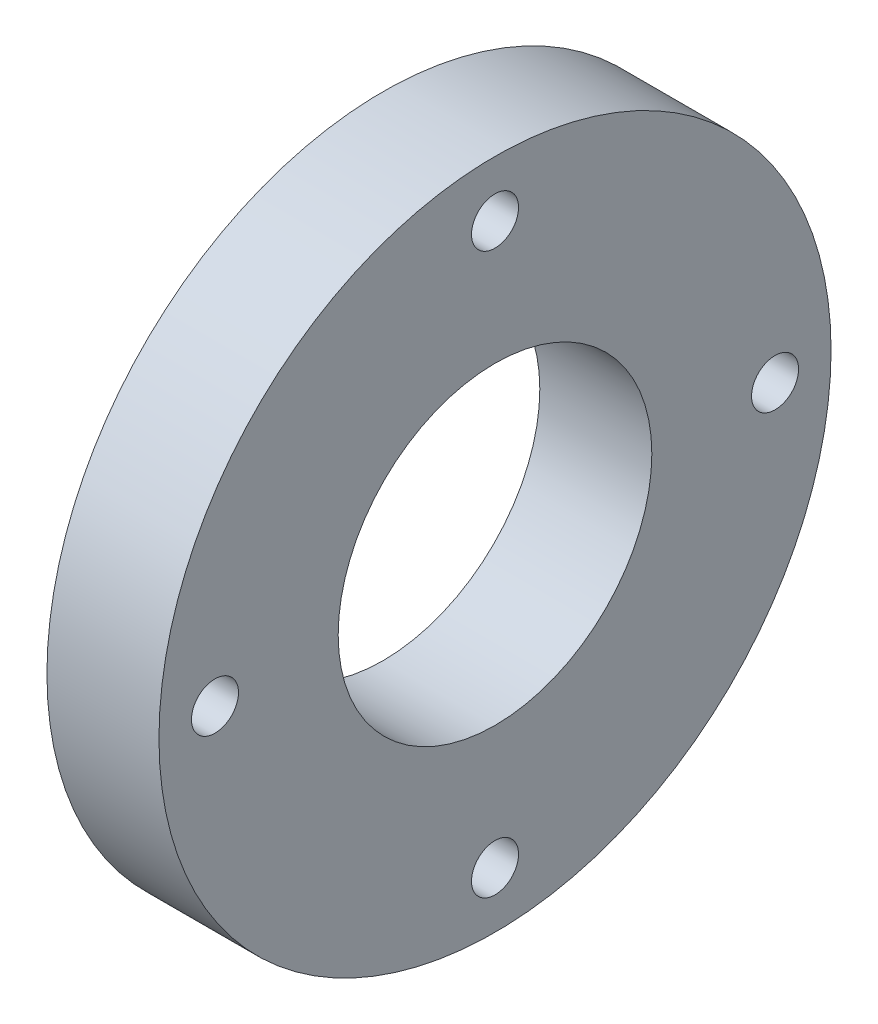
SolidWorks part; units mm, degrees
ref_plane "Front Plane" through (0, 0, 0) normal (0, 0, 1) x (1, 0, 0)
ref_plane "Top Plane" through (0, 0, 0) normal (0, 1, 0) x (1, 0, 0)
ref_plane "Right Plane" through (0, 0, 0) normal (1, 0, 0) x (0, 0, -1)
sketch "Sketch1" plane through (0, 0, 0) normal (0, 0, 1) x (1, 0, 0)
  line L0 (21, 15) -> (21, 0)
  line L1 (21, 0) -> (26, 0)
  line L2 (26, 0) -> (26, 15)
  line L3 (26, 15) -> (21, 15)
  line L4 (21, 0) -> (26, 0) construction
revolve "Revolve1" add sketch "Sketch1" angle 360 about L4 reverse direction yes
hole_wizard "Ø14.0 (14) Diameter Hole1" positions "Sketch3" profile "Sketch2" hole size "Ø14.0" standard "ANSI Metric"
sketch "Sketch3" plane through (21, 0, 0) normal (-1, 0, 0) x (0, 0, 1)
  point P0 (0, 0)
sketch "Sketch2" plane through (21, 0, 0) normal (0, 1, 0) x (0, 0, 1)
  line L0 (0, 0) -> (0, 5)
  line L1 (0, 5) -> (7, 5)
  line L2 (7, 5) -> (7, 0)
  line L5 (7, 0) -> (0, 0)
  line L11 (0, -6.35) -> (0, 107.95) construction
  dimension "Thru Hole Dia." = 14
  dimension "Thru Hole Depth" = 5
hole_wizard "Ø2.1 (2.1) Diameter Hole1" positions "Sketch5" profile "Sketch4" hole size "Ø2.1" standard "ANSI Metric"
sketch "Sketch5" plane through (26, 0, 0) normal (1, 0, 0) x (0, 0, -1)
  point P0 (-12.5, 0)
  point P1 (12.5, 0)
  point P2 (0, -12.5)
  point P3 (0, 12.5)
sketch "Sketch4" plane through (26, 0, 12.5) normal (0, 1, 0) x (0, 0, -1)
  line L0 (0, 0) -> (0, 2.5)
  line L1 (0, 2.5) -> (1.05, 2.5)
  line L2 (1.05, 2.5) -> (1.05, 0)
  line L5 (1.05, 0) -> (0, 0)
  line L10 (0, 2.5) -> (-1.05, 2.5) construction
  line L11 (0, -6.35) -> (0, 107.95) construction
  dimension "Hole Dia." = 2.1
  dimension "Hole Depth" = 2.5
  dimension "Drill Angle" = 180
